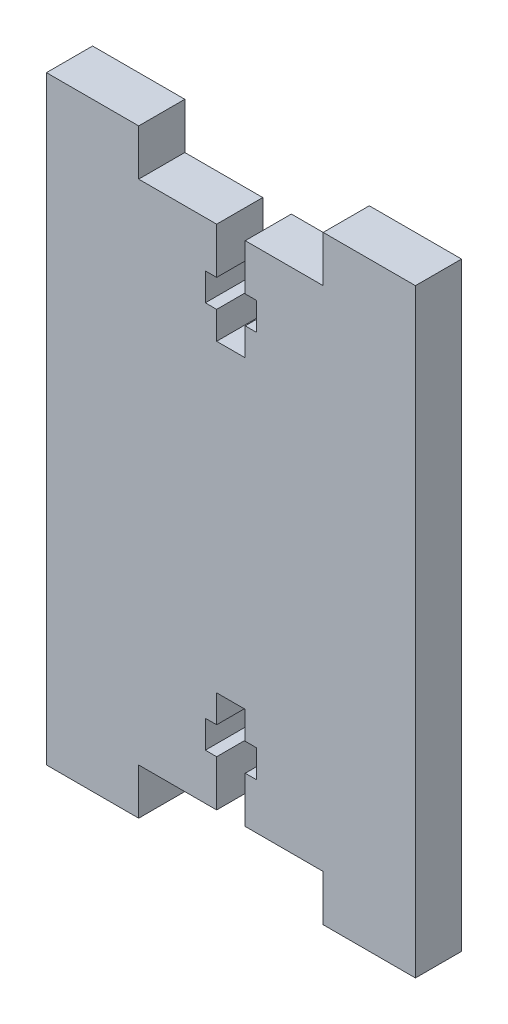
SolidWorks part; units mm, degrees
ref_plane "Plan de face" through (0, 0, 0) normal (0, 0, 1) x (1, 0, 0)
ref_plane "Plan de dessus" through (0, 0, 0) normal (0, 1, 0) x (1, 0, 0)
ref_plane "Plan de droite" through (0, 0, 0) normal (1, 0, 0) x (0, 0, -1)
ref_plane "Plan1" through (0, 0, 5) normal (0, 0, 1) x (1, 0, 0)
sketch "Esquisse1" plane through (0, 0, 5) normal (0, 0, 1) x (1, 0, 0)
  line L0 (20, 31) -> (-20, 31)
  line L1 (-20, 31) -> (-20, -31)
  line L2 (-20, -31) -> (20, -31)
  line L3 (20, -31) -> (20, 31)
extrude "Boss.-Extru.1" add sketch "Esquisse1" against normal blind 5
sketch "Esquisse2" plane through (0, 0, 0) normal (0, 0, -1) x (-1, 0, 0)
  line L0 (10, 31) -> (-10, 31)
  line L1 (-10, 31) -> (-10, 27.5)
  line L2 (-10, 27.5) -> (10, 27.5)
  line L3 (10, 27.5) -> (10, 31)
extrude "Enlèv. mat.-Extru.1" cut sketch "Esquisse2" against normal through all
sketch "Esquisse3" plane through (0, 0, 0) normal (0, 0, -1) x (-1, 0, 0)
  line L0 (-10, -31) -> (10, -31)
  line L1 (10, -31) -> (10, -27.5)
  line L2 (10, -27.5) -> (-10, -27.5)
  line L3 (-10, -27.5) -> (-10, -31)
extrude "Enlèv. mat.-Extru.2" cut sketch "Esquisse3" against normal through all
sketch "Esquisse8" plane through (0, 0, 5) normal (0, 0, 1) x (1, 0, 0)
  line L8 (-10, -27.5) -> (10, -27.5) construction
  line L9 (-1.55, -27.5) -> (1.55, -27.5)
  line L10 (-1.55, -27.5) -> (-1.55, -16.5)
  line L11 (-1.55, -16.5) -> (1.55, -16.5)
  line L12 (1.55, -27.5) -> (1.55, -16.5)
  line L13 (0, 0) -> (11.7651, 0) construction
  line L14 (-2.775, -19.5) -> (2.775, -19.5)
  line L15 (-2.775, -19.5) -> (-2.775, -22.5)
  line L16 (-2.775, -22.5) -> (2.775, -22.5)
  line L17 (2.775, -19.5) -> (2.775, -22.5)
  line L18 (2.775, 19.5) -> (2.775, 22.5)
  line L19 (-2.775, 22.5) -> (2.775, 22.5)
  line L20 (-2.775, 19.5) -> (-2.775, 22.5)
  line L21 (-2.775, 19.5) -> (2.775, 19.5)
  line L22 (1.55, 27.5) -> (1.55, 16.5)
  line L23 (-1.55, 16.5) -> (1.55, 16.5)
  line L24 (-1.55, 27.5) -> (-1.55, 16.5)
  line L25 (-1.55, 27.5) -> (1.55, 27.5)
  line L27 (10, -27.5) -> (10, -31) construction
  line M13 (10, 27.5) -> (-10, 27.5)
  line M19 (-10, -27.5) -> (10, -27.5)
  dimension "D1" = 3.1
  dimension "D2" = 5
  dimension "D3" = 3
  dimension "D4" = 3
  dimension "D5" = 5.55
  dimension "D6" = 1.225
  dimension "D7" = 8.45
extrude "Enlèv. mat.-Extru.3" cut sketch "Esquisse8" against normal through all contours L19 L24 L21 L22 | L24 L19 L22 M13 | L24 L19 L20 L21 | L19 L22 L21 L18 | L21 L24 L23 L22 | L10 L14 L12 L11 | L15 L16 L10 L14 | L10 L16 L12 L14 | L17 L14 L12 L16 | L16 L10 L12 M19 region at (0, -25, 5) region at (-2.1625, -21, 5) region at (0, -21, 5) region at (2.1625, -21, 5) region at (0, -18, 5) region at (2.1625, 21, 5) region at (0, 18, 5) region at (0, 21, 5) region at (0, 25, 5) region at (-2.1625, 21, 5)
sketch "Esquisse9" plane through (0, 0, 5) normal (0, 0, 1) x (1, 0, 0)
  line L0 (-20, 31) -> (-20, -31) construction
  line L1 (-20, 32.5) -> (-10, 32.5)
  line L2 (-20, 32.5) -> (-20, -32.5)
  line L3 (-20, -32.5) -> (-10, -32.5)
  line L4 (-10, 32.5) -> (-10, -32.5)
  line L5 (20, 32.5) -> (10, 32.5)
  line L6 (20, 32.5) -> (20, -32.5)
  line L7 (20, -32.5) -> (10, -32.5)
  line L8 (10, 32.5) -> (10, -32.5)
  line L9 (-10, 27.5) -> (-10, 31) construction
  line L10 (-1.55, 27.5) -> (-10, 27.5) construction
  line L11 (-10, -27.5) -> (-1.55, -27.5) construction
  line L12 (1.55, -27.5) -> (10, -27.5) construction
  line L13 (20, -31) -> (20, 31) construction
  line L15 (10, 27.5) -> (1.55, 27.5) construction
  line L16 (10, 31) -> (10, 27.5) construction
  dimension "D1" = 0
  dimension "D2" = 0
  dimension "D3" = 5
  dimension "D4" = 5
  dimension "D5" = 5
  dimension "D6" = 0
  dimension "D7" = 5
  dimension "D8" = 0
extrude "Boss.-Extru.2" add sketch "Esquisse9" against normal blind 5
